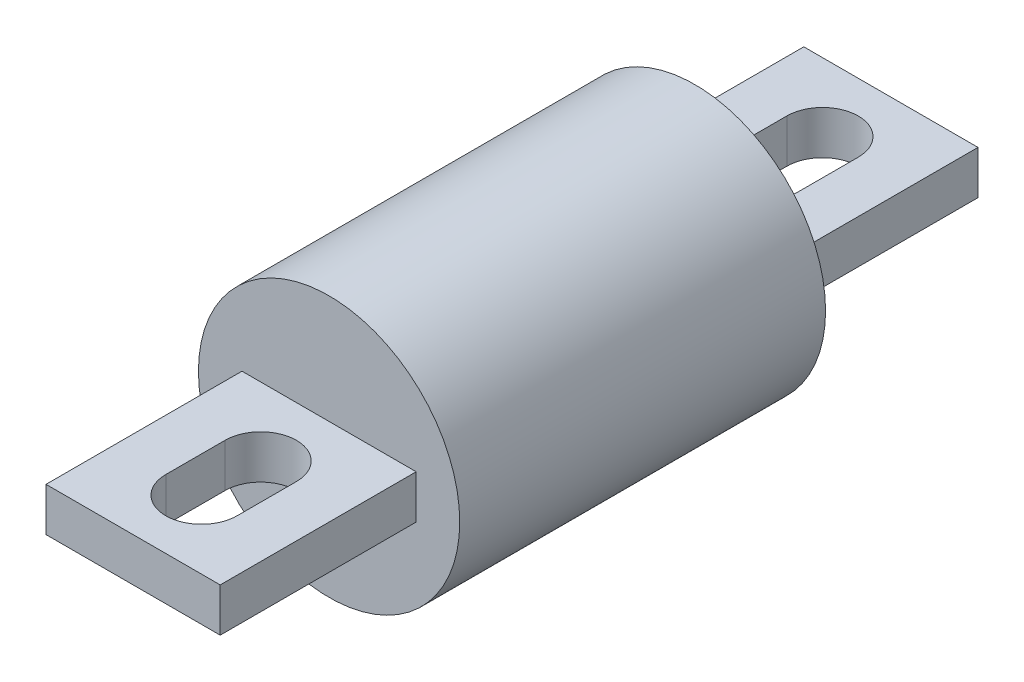
SolidWorks part; units mm, degrees
ref_plane "Front Plane" through (0, 0, 0) normal (0, 0, 1) x (1, 0, 0)
ref_plane "Top Plane" through (0, 0, 0) normal (0, 1, 0) x (1, 0, 0)
ref_plane "Right Plane" through (0, 0, 0) normal (1, 0, 0) x (0, 0, -1)
sketch "Sketch1" plane through (0, 0, 0) normal (0, 0, 1) x (1, 0, 0)
  circle A0 centre (0, 0) radius 19.05
  dimension "D1" = 38.1
extrude "Fuse" add sketch "Sketch1" along normal blind 26.67 and the other way blind 26.67
sketch "Sketch2" plane through (0, 0, 0) normal (0, 1, 0) x (1, 0, 0)
  line L0 (19.05, 26.67) -> (-19.05, 26.67) construction
  line L1 (-12.7, 26.67) -> (12.7, 26.67)
  line L2 (-12.7, 26.67) -> (-12.7, 55.245)
  line L3 (-12.7, 55.245) -> (12.7, 55.245)
  line L4 (12.7, 26.67) -> (12.7, 55.245)
  line L5 (0, 36.6395) -> (0, 45.2755) construction
  line L6 (-5.207, 36.6395) -> (-5.207, 45.2755)
  line L7 (5.207, 36.6395) -> (5.207, 45.2755)
  arc A0 (-5.207, 36.6395) -> (5.207, 36.6395) centre (0, 36.6395) ccw
  arc A1 (5.207, 45.2755) -> (-5.207, 45.2755) centre (0, 45.2755) ccw
  point P6 (0, 55.245)
  point P12 (0, 40.9575)
  point P17 (12.7, 40.9575)
  dimension "D3" = 5.207
  dimension "D4" = 19.05
  dimension "D1" = 25.4
  dimension "D2" = 28.575
extrude "Tab" add sketch "Sketch2" along normal blind 3.175 and the other way blind 3.175
mirror "Tab Mirror" about plane through (0, 0, 0) normal (0, 0, 1) of "Tab"
